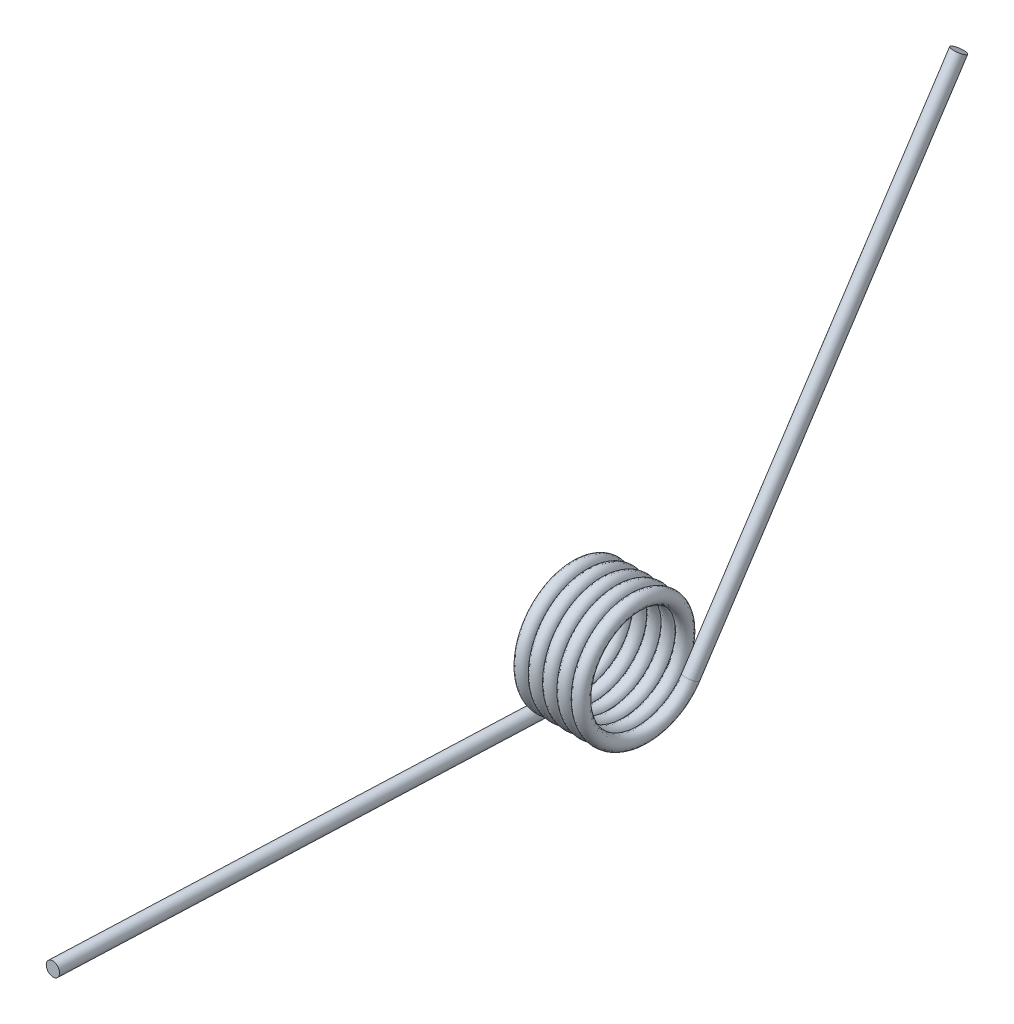
SolidWorks part; units mm, degrees
ref_plane "Front" through (0, 0, 0) normal (0, 0, 1) x (1, 0, 0)
ref_plane "Top" through (0, 0, 0) normal (0, 1, 0) x (1, 0, 0)
ref_plane "Right" through (0, 0, 0) normal (1, 0, 0) x (0, 0, -1)
sketch "Sketch1" plane through (0, 0, 0) normal (1, 0, 0) x (0, 0, -1)
  line L0 (0, 0) -> (0, -3.1115) construction
  line L1 (0, -3.1115) -> (0, -3.556) construction
  line L2 (0, -3.556) -> (0, -4.0005) construction
  line L3 (0, 4.0005) -> (0, -4.0005) construction
  circle A0 centre (0, 0) radius 3.1115 construction
  circle A1 centre (0, 0) radius 4.0005 construction
  circle A2 centre (0, 0) radius 3.556
  circle A3 centre (0, -3.556) radius 0.4445 construction
  circle A4 centre (0, 0) radius 2.3749 construction
  dimension "Wire Dia" = 0.889
  dimension "Spring OD" = 8.001
  dimension "Max Rod OD" = 4.7498
curve "Helix/Spiral1" pitch 0.9144 height 4.7244 turns 5.1667
ref_plane "Plane1" through (0, -3.556, 0) normal (0.0409, 0, -0.9992) x (0.9952, 0.0889, 0.0407)
sketch "Sketch2" plane through (0, -3.556, 0) normal (0.0409, 0, -0.9992) x (0.9952, 0.0889, 0.0407)
  circle A0 centre (0, 0) radius 0.4445
  dimension "D1" = 0.889
sweep "Sweep1" add profiles "Sketch2" path "Helix/Spiral1"
sketch "Sketch3" plane through (0, 0, 0) normal (-0.0409, 0, 0.9992) x (-0.9952, -0.0889, -0.0407)
  circle A1 centre (0.3161, 3.5419) radius 0.4445
  circle A2 centre (0.3161, 3.5419) radius 0.4445
  dimension "D1" = 0
extrude "Extrude1" add sketch "Sketch3" along normal blind 31.75
sketch "Sketch4" plane through (0.0079, 0.1672, -0.0965) normal (0.0409, 0.8653, -0.4996) x (0.9927, -0.0919, -0.078)
  circle A1 centre (5.0935, 2.9974) radius 0.4445
  circle A2 centre (5.0935, 2.9974) radius 0.4445
  dimension "D1" = 0
extrude "Extrude2" add sketch "Sketch4" along normal blind 31.75
sketch "Sketch5" plane through (0, 0, 0) normal (1, 0, 0) x (0, 0, -1)
  line L0 (-31.7234, -3.1115) -> (-31.7234, -4.0005) construction
  circle A0 centre (0, 0) radius 2.3749 construction
  circle A1 centre (0, 0) radius 2.3749
equation "\"D4@Helix/Spiral1\"=\"Wire Dia@Sketch1\"+.001"
equation "\"D1@Sketch2\"=\"Wire Dia@Sketch1\""
equation "\"D1@Extrude2\"=\"Leg Length@Extrude1\""
